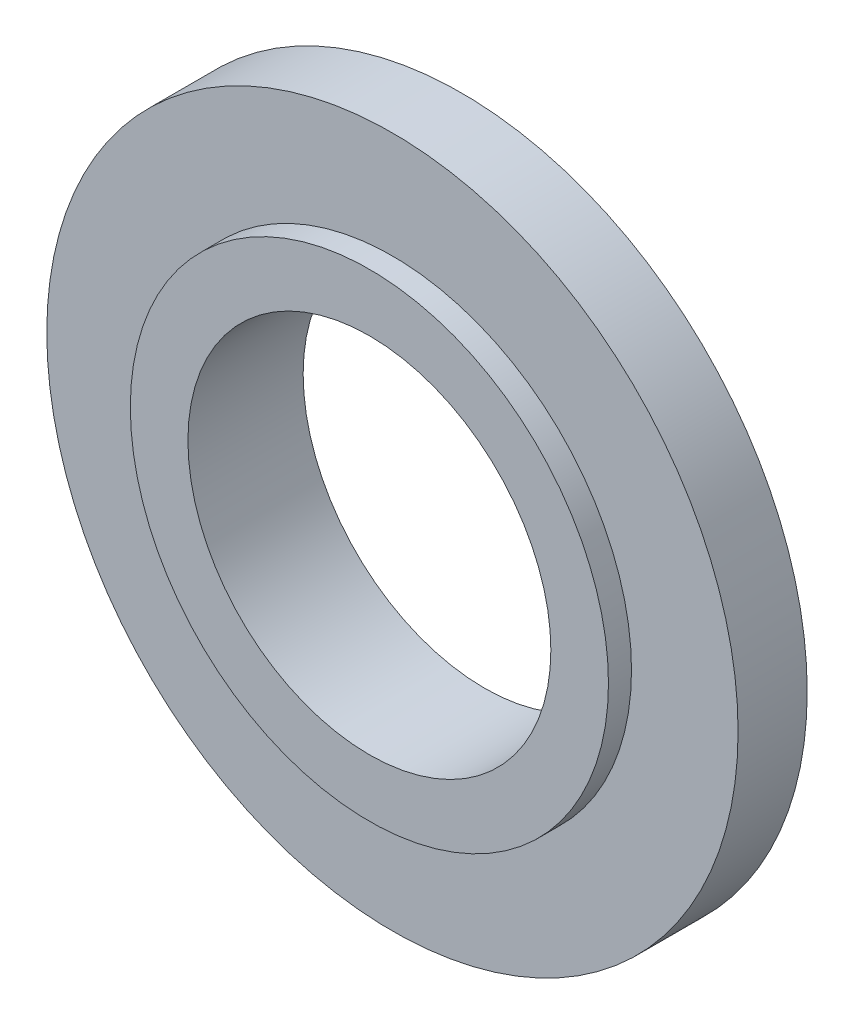
SolidWorks part; units mm, degrees
ref_plane "正面" through (0, 0, 0) normal (0, 0, 1) x (1, 0, 0)
ref_plane "平面" through (0, 0, 0) normal (0, 1, 0) x (1, 0, 0)
ref_plane "右側面" through (0, 0, 0) normal (1, 0, 0) x (0, 0, -1)
sketch "ｽｹｯﾁ1" plane through (0, 0, 0) normal (0, 0, 1) x (1, 0, 0)
  circle A0 centre (0, 0) radius 6
  circle A1 centre (0, 0) radius 3.15
  dimension "D1" = 6.3
  dimension "D2" = 12
extrude "ﾎﾞｽ - 押し出し1" add sketch "ｽｹｯﾁ1" along normal blind 2
sketch "ｽｹｯﾁ2" plane through (0, 0, 2) normal (0, 0, 1) x (1, 0, 0)
  circle A0 centre (0, 0) radius 4.15
  circle A1 centre (0, 0) radius 6
  circle A2 centre (0, 0) radius 6
  circle A3 centre (0, 0) radius 3.15 construction
  dimension "D2" = 1
  dimension "D1" = 0
extrude "ｶｯﾄ - 押し出し1" cut sketch "ｽｹｯﾁ2" against normal blind 0.4
extrude "ｶｯﾄ - 押し出し2" cut sketch "ｽｹｯﾁ2<2>" along normal blind 0.4 from surface starting at face at (6, 0, 0)
sketch "ｽｹｯﾁ2<2>" plane through (0, 0, 2) normal (0, 0, 1) x (1, 0, 0) same geometry as "ｽｹｯﾁ2"
